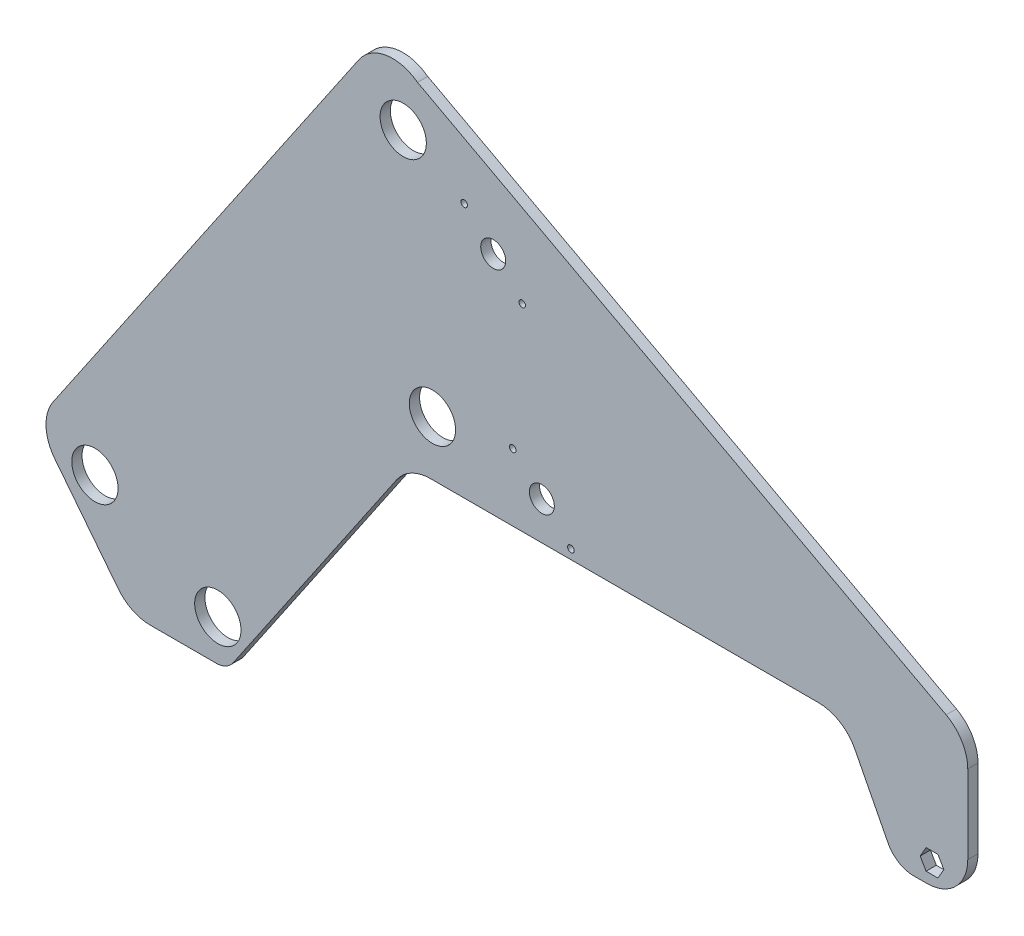
SolidWorks part; units mm, degrees
other "Markup1"
sketch "Sketch1" plane through (-441.7893, 331.8239, 6.35) normal (-0.0431, 0.0102, 0.999) x (0.9985, 0.0354, 0.0427)
sketch "Sketch2" plane through (-413.6701, 343.933, 6.35) normal (-0.0431, 0.0102, 0.999) x (0.9985, 0.0354, 0.0427)
sketch "Sketch3" plane through (-436.3774, 318.5567, 6.35) normal (-0.0431, 0.0102, 0.999) x (0.9985, 0.0354, 0.0427)
sketch "Sketch5" plane through (-436.3774, 318.5567, 6.35) normal (-0.0431, 0.0102, 0.999) x (0.9985, 0.0354, 0.0427)
sketch "Sketch7" plane through (-430.3226, 318.5567, 6.35) normal (-0.0431, 0.0102, 0.999) x (0.9985, 0.0354, 0.0427)
sketch "Sketch9" plane through (-430.3226, 318.5567, 6.35) normal (-0.0431, 0.0102, 0.999) x (0.9985, 0.0354, 0.0427)
sketch "Sketch11" plane through (-430.3226, 318.5567, 6.35) normal (-0.0431, 0.0102, 0.999) x (0.9985, 0.0354, 0.0427)
other "Markup2"
sketch "Sketch4" plane through (102.4721, 318.5567, 6.35) normal (0.9364, 0.1073, 0.3342) x (0.3416, -0.0598, -0.9379)
sketch "Sketch6" plane through (102.4721, 318.5567, 6.35) normal (0.9364, 0.1073, 0.3342) x (0.3416, -0.0598, -0.9379)
sketch "Sketch8" plane through (141.2086, 318.5567, 6.35) normal (0.9364, 0.1073, 0.3342) x (0.3416, -0.0598, -0.9379)
sketch "Sketch10" plane through (141.2086, 318.5567, 6.35) normal (0.9364, 0.1073, 0.3342) x (0.3416, -0.0598, -0.9379)
sketch "Sketch12" plane through (141.2086, 318.5567, 6.35) normal (0.9364, 0.1073, 0.3342) x (0.3416, -0.0598, -0.9379)
material "Lexan"
ref_plane "Front Plane" through (0, 0, 0) normal (0, 0, 1) x (1, 0, 0)
ref_plane "Top Plane" through (0, 0, 0) normal (0, 1, 0) x (1, 0, 0)
ref_plane "Right Plane" through (0, 0, 0) normal (1, 0, 0) x (0, 0, -1)
sketch "Model" plane through (0, 0, 0) normal (0, 0, 1) x (1, 0, 0)
  line L1 (-191.9011, 104.6502) -> (-112.96, 104.6502)
  line L3 (-314.2383, -55.3595) -> (-212.8994, 93.5413)
  line L4 (-236.3032, 307.4477) -> (-425.9209, 28.8361)
  line L5 (-424.8981, -1.1437) -> (-385.5815, -51.2028)
  line L13 (126.3831, 53.8502) -> (122.717, 60.2002)
  line L14 (122.717, 60.2002) -> (115.3846, 60.2002)
  line L15 (115.3846, 60.2002) -> (111.7185, 53.8502)
  line L16 (111.7185, 53.8502) -> (115.3846, 47.5002)
  line L17 (115.3846, 47.5002) -> (122.717, 47.5002)
  line L18 (122.717, 47.5002) -> (126.3831, 53.8502)
  line L19 (-365.606, -60.914) -> (-324.7375, -60.914)
  line L20 (-871.0211, -88.854) -> (370.1019, -88.854) construction
  line L22 (141.2086, 66.5502) -> (141.2086, 78.8846)
  line L27 (107.6196, 41.1502) -> (115.8086, 41.1502)
  line L28 (-399.9752, 2.586) -> (-323.7752, -35.514) construction
  line L29 (-323.7752, -35.514) -> (-190.7071, 138.5169) construction
  line L30 (-190.7071, 138.5169) -> (-208.8329, 283.4378) construction
  line L31 (-208.8329, 283.4378) -> (-399.9752, 2.586) construction
  line L32 (91.8004, 50.8135) -> (71.26, 90.8456)
  line L33 (48.6612, 104.6502) -> (-11.3966, 104.6502)
  line L34 (141.2086, 78.8846) -> (141.2086, 115.3033)
  line L35 (127.8091, 137.6897) -> (-86.3327, 252.4836)
  line L36 (-171.0363, 260.7567) -> (-135.0085, 260.7567) construction
  line L37 (-135.0085, 260.7567) -> (-135.0085, 224.9427)
  line L38 (-171.0363, 260.7567) -> (-135.0085, 224.9427)
  line L39 (-171.0363, 260.7567) -> (-153.0224, 260.7567)
  line L40 (-68.51, 104.6502) -> (-2.1388, 104.6502)
  line L41 (-122.3008, 271.7648) -> (-199.9496, 313.3896)
  line L42 (-122.3008, 271.7648) -> (-86.3327, 252.4836)
  line L43 (-112.96, 104.6502) -> (-68.51, 104.6502)
  line L44 (-153.0224, 260.7567) -> (-153.0224, 244.7547)
  line L45 (-140.9024, 144.2514) -> (-104.8747, 144.2514) construction
  line L46 (-104.8747, 144.2514) -> (-104.8747, 108.4374)
  line L47 (-140.9024, 144.2514) -> (-104.8747, 108.4374)
  line L48 (-140.9024, 144.2514) -> (-122.8885, 144.2514)
  line L49 (-122.8885, 144.2514) -> (-122.8885, 128.2494)
  arc A3 (121.2475, 59.8082) -> (121.352, 60.2002) centre (96.7586, 66.5502) ccw
  circle A9 centre (-323.7752, -35.514) radius 14.351
  circle A10 centre (-399.9752, 2.586) radius 14.351
  circle A12 centre (-190.7071, 138.5169) radius 14.351
  arc A15 (107.6196, 41.1502) -> (91.8004, 50.8135) centre (107.6196, 58.9302) cw
  arc A21 (-191.9011, 104.6502) -> (-212.8994, 93.5413) centre (-191.9011, 79.2502) ccw
  circle A22 centre (-208.8329, 283.4378) radius 14.351
  circle A24 centre (119.0508, 53.8502) radius 6.35 construction
  arc A31 (-324.7375, -60.914) -> (-314.2383, -55.3595) centre (-324.7375, -48.214) ccw
  arc A40 (114.7422, 48.6129) -> (115.0458, 48.9225) centre (96.7586, 66.5502) ccw
  arc A43 (115.8086, 41.1502) -> (141.2086, 66.5502) centre (115.8086, 66.5502) ccw
  arc A44 (-236.3032, 307.4477) -> (-199.9496, 313.3896) centre (-215.305, 293.1567) cw
  arc A45 (-365.606, -60.914) -> (-385.5815, -51.2028) centre (-365.606, -35.514) cw
  arc A46 (71.26, 90.8456) -> (48.6612, 104.6502) centre (48.6612, 79.2502) ccw
  arc A47 (141.2086, 115.3033) -> (127.8091, 137.6897) centre (115.8086, 115.3033) ccw
  arc A48 (-424.8981, -1.1437) -> (-425.9209, 28.8361) centre (-404.9226, 14.5451) cw
  circle A51 centre (-171.0363, 262.7887) radius 2.032
  circle A52 centre (-135.0085, 226.9747) radius 2.032
  circle A53 centre (-153.0224, 244.7547) radius 7.747
  circle A54 centre (-140.9024, 146.2834) radius 2.032
  circle A55 centre (-104.8747, 110.4694) radius 2.032
  circle A56 centre (-122.8885, 128.2494) radius 7.747
  ellipse E0 centre (-551.1692, 173.9527) end of major axis (-591.2054, 216.0961) minor radius 17.278
  point P31 (-177.5612, 330.9695)
  point P34 (100.2935, -12.8222)
  point P43 (-377.9543, -60.914)
  point P55 (96.7586, 41.1502)
  point P59 (174.831, 53.8502)
  point P60 (-205.3388, 104.6502)
  point P64 (-436.3774, 13.472)
  point P91 (-152.7676, 153.6641)
  point P92 (-160.5704, 143.2255)
  point P93 (-127.1095, 110.3434)
  point P94 (-115.8531, 110.0654)
  point P95 (-132.2513, 144.5294)
  point P96 (-104.8747, 144.2514)
  dimension "D3" = 38.1
  dimension "D4" = 104.6502
  dimension "D5" = 76.2
  dimension "D6" = 44.45
  dimension "D7" = 12.7
  dimension "D8" = 28.702
  dimension "D11" = 139.7
  dimension "D12" = 27.94
  dimension "D21" = 124.238
  dimension "D13" = 12.7
  dimension "D16" = 355.6
  dimension "D23" = 25.4
  dimension "D24" = 25.4
  dimension "D26" = 25.4
  dimension "D14" = 406.4
  dimension "D20" = 254
  dimension "D29" = 25.4
  dimension "D31" = 25.4
  dimension "D25" = 88.9
  dimension "D30" = 17.78
  dimension "D32" = 25.4
  dimension "D33" = 25.4
  dimension "D34" = 35.814
  dimension "D35" = 50.8
  dimension "D37" = 4.064
  dimension "D38" = 4.064
  dimension "D39" = 15.494
  dimension "D42" = 4.064
  dimension "D43" = 15.494
  dimension "D44" = 4.064
  dimension "D9" = 19.05
  dimension "D10" = 146.05
  dimension "D15" = 33.8667
  dimension "D17" = 339.725
  dimension "D18" = 219.075
  dimension "D19" = 50.8
  dimension "D22" = 25.4
  dimension "D27" = 53.2168
  dimension "D28" = 12.7
  dimension "D36" = 16.002
  dimension "D40" = 35.814
  dimension "D41" = 16.002
  dimension "D45" = 50.8
extrude "Boss-Extrude1" add sketch "Model" along normal blind 6.35 contours A48 L5 A45 L19 A31 L3 A21 L1 L43 L40 L33 A46 L32 A15 L27 A43 L22 L34 A47 L35 L42 L41 A44 L4 A56 L47 A54 L48 L49 A55 A53 L38 A51 L39 L44 A52 | A56 L49 L48 L47 | A53 L44 L39 L38 region at (-206.9871, 107.7659, 0) region at (-160.0611, 256.5181, 0) region at (-129.9272, 140.0129, 0)
